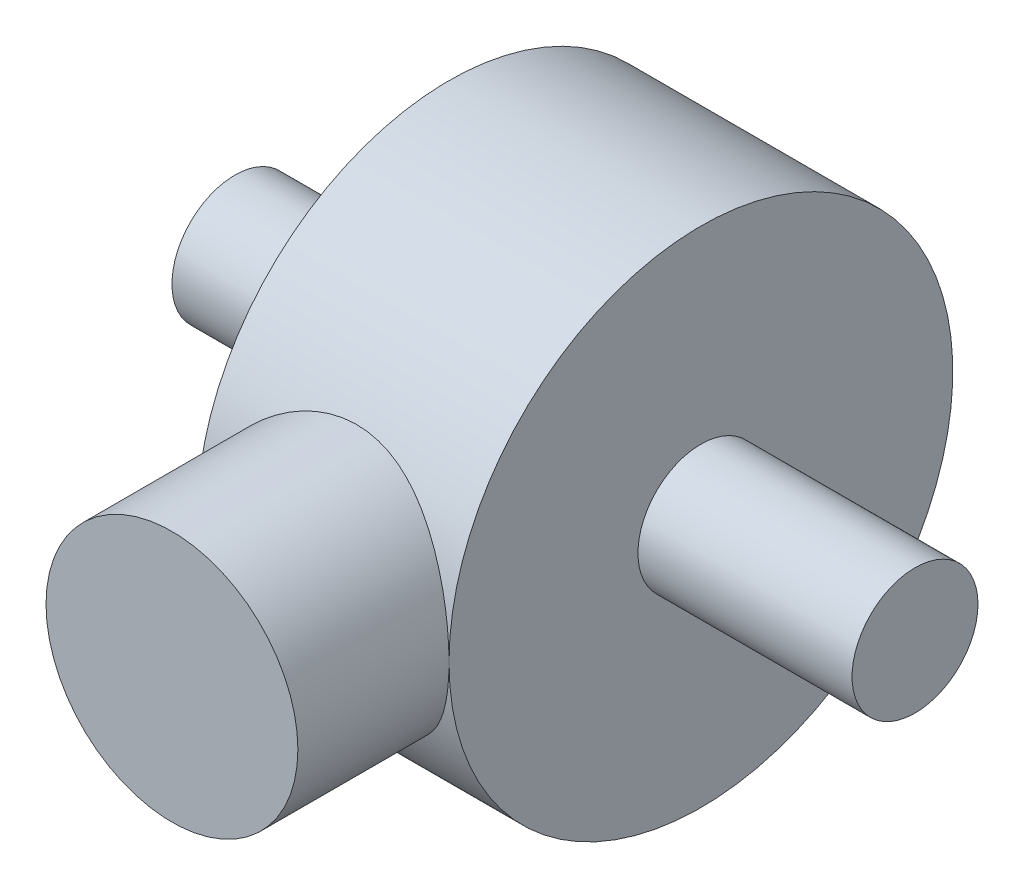
SolidWorks part; units mm, degrees
ref_plane "Alzado" through (0, 0, 0) normal (0, 0, 1) x (1, 0, 0)
ref_plane "Planta" through (0, 0, 0) normal (0, 1, 0) x (1, 0, 0)
ref_plane "Vista lateral" through (0, 0, 0) normal (1, 0, 0) x (0, 0, -1)
sketch "Croquis1" plane through (0, 0, 0) normal (1, 0, 0) x (0, 0, -1)
  circle A0 centre (0, 0) radius 25.4
  dimension "D1" = 50.8
extrude "Saliente-Extruir1" add sketch "Croquis1" along normal mid plane 25.4
ref_plane "Plano1" through (0, 0, 40.64) normal (0, 0, 1) x (1, 0, 0)
sketch "Croquis2" plane through (0, 0, 40.64) normal (0, 0, 1) x (1, 0, 0)
  circle A0 centre (0, 0) radius 12.7
extrude "Saliente-Extruir2" add sketch "Croquis2" against normal up to surface (15.24 mm away) up to face at (12.7, 0, -25.4)
sketch "Croquis6" plane through (0, 0, 0) normal (1, 0, 0) x (0, 0, -1)
  circle A0 centre (0, 0) radius 6.35
  dimension "D1" = 12.7
extrude "Saliente-Extruir5" add sketch "Croquis6" along normal mid plane 68.58
ref_axis "Joint6" through (0, 0, 21.1625) along (0, 0, 1)
ref_plane "基准面1" through (0, 0, 0) normal (1, 0, 0) x (0, 0, -1)
